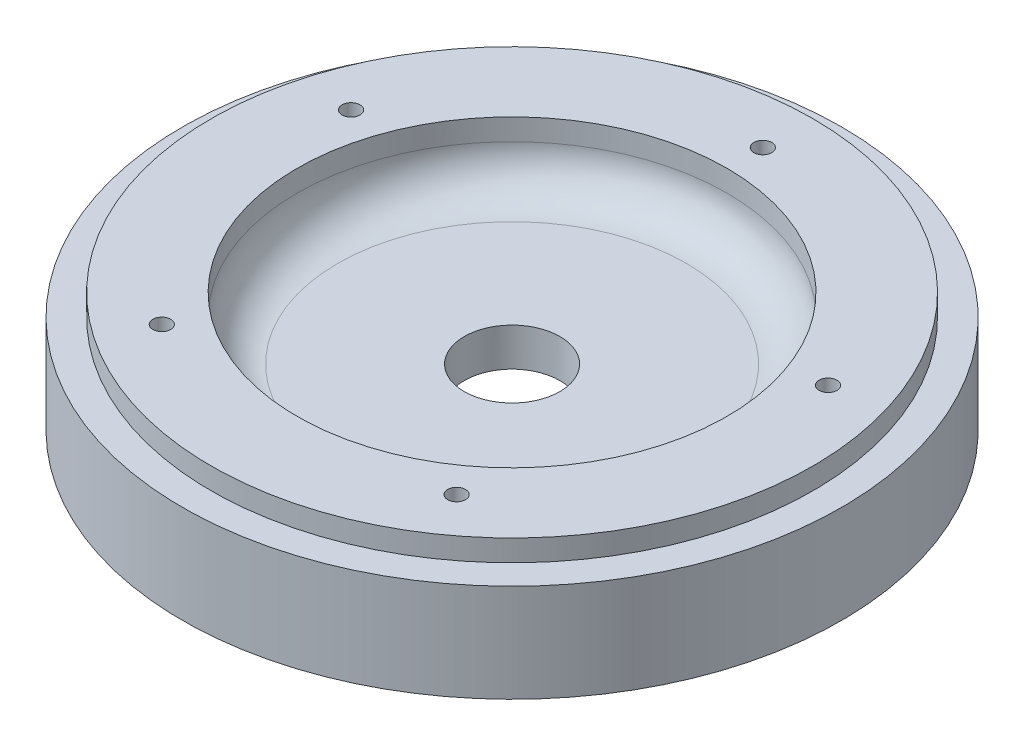
SolidWorks part; units mm, degrees
ref_plane "Front Plane" through (0, 0, 0) normal (0, 0, 1) x (1, 0, 0)
ref_plane "Top Plane" through (0, 0, 0) normal (0, 1, 0) x (1, 0, 0)
ref_plane "Right Plane" through (0, 0, 0) normal (1, 0, 0) x (0, 0, -1)
sketch "Sketch1" plane through (0, 0, 0) normal (0, 0, 1) x (1, 0, 0)
  line L0 (87.63, 0) -> (57.15, 0)
  line L1 (57.15, 0) -> (57.15, 5.08)
  line L2 (57.15, 5.08) -> (0, 5.08)
  line L3 (0, 5.08) -> (0, 15.24)
  line L4 (0, 15.24) -> (57.15, 15.24)
  line L5 (57.15, 15.24) -> (57.15, 31.75)
  line L6 (57.15, 31.75) -> (79.9973, 31.75)
  line L7 (79.9973, 31.75) -> (79.9973, 26.035)
  line L8 (79.9973, 26.035) -> (87.63, 26.035)
  line L9 (87.63, 26.035) -> (87.63, 0)
  point P10 (0, 10.16)
  dimension "D1" = 10.16
  dimension "D2" = 87.63
  dimension "D3" = 57.15
  dimension "D4" = 57.15
  dimension "D5" = 31.75
  dimension "D6" = 5.715
  dimension "D7" = 79.9973
  dimension "D8" = 20.955
revolve "Revolve1" add sketch "Sketch1" angle 360 about L3
hole_wizard "1 (1) Diameter Hole1" positions "Sketch2" profile "Sketch4" hole size "1" standard "ANSI Inch" end condition through all
sketch "Sketch2" plane through (0, 15.24, 0) normal (0, 1, 0) x (1, 0, 0)
  point P0 (0, 0)
sketch "Sketch4" plane through (0, 15.24, 0) normal (1, 0, 0) x (0, 0, 1)
  line L0 (0, 0) -> (0, 15.24)
  line L1 (0, 15.24) -> (12.7, 15.24)
  line L2 (12.7, 15.24) -> (12.7, 0)
  line L5 (12.7, 0) -> (0, 0)
  line L11 (0, -6.35) -> (0, 107.95) construction
  dimension "Thru Hole Dia." = 25.4
  dimension "Thru Hole Depth" = 15.24
hole_wizard "3/16 (0.1865) Dowel Hole1" positions "Sketch5" profile "Sketch7" hole size "3/16" standard "ANSI Inch"
sketch "Sketch5" plane through (0, 31.75, 0) normal (0, 1, 0) x (1, 0, 0)
  point P0 (0, 66.675)
  dimension "D1" = 66.675
sketch "Sketch7" plane through (0, 31.75, -66.675) normal (1, 0, 0) x (0, 0, 1)
  line L0 (0, 0) -> (0, 14.1232)
  line L1 (0, 14.1232) -> (2.3685, 12.7)
  line L2 (2.3685, 12.7) -> (2.3685, 0)
  line L5 (2.3685, 0) -> (0, 0)
  line L10 (0, 14.1232) -> (-2.3686, 12.7) construction
  line L11 (0, -6.35) -> (0, 107.95) construction
  dimension "Hole Dia." = 4.7371
  dimension "Hole Depth" = 12.7
  dimension "Drill Angle" = 118
pattern_circular "CirPattern1" count 5 over 360 about axis through (0, 31.75, 0) along (0, -1, 0) of "3/16 (0.1865) Dowel Hole1"
fillet "Fillet2" radius 10.795 2 edges at (0, 5.08, -57.15) (0, 15.24, -57.15)
